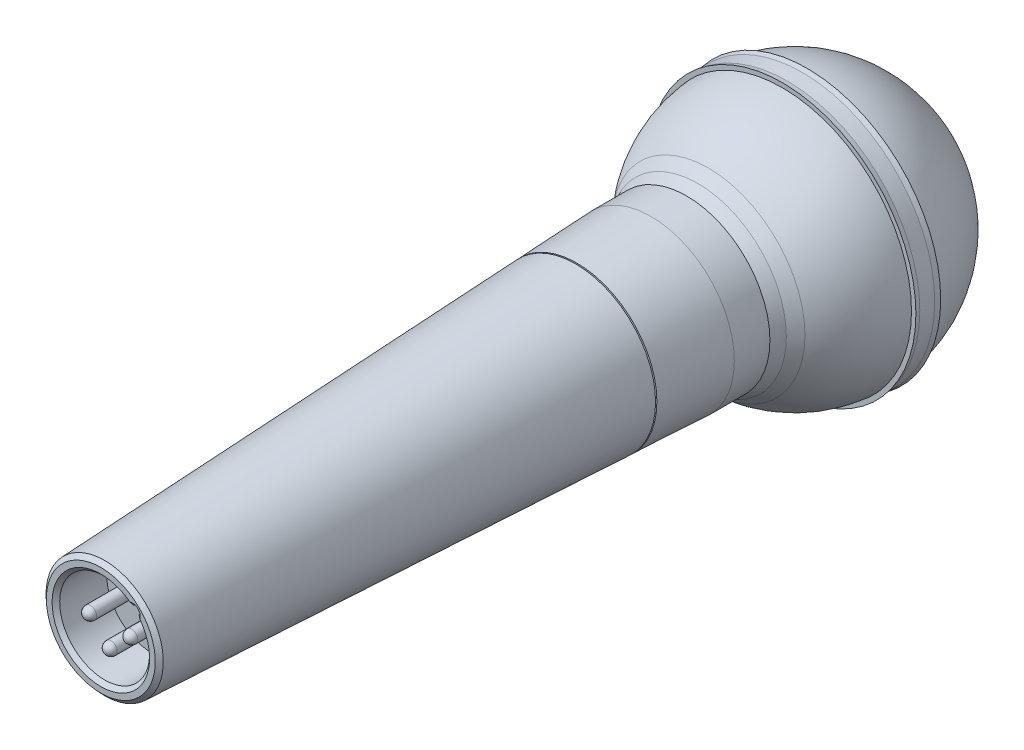
SolidWorks part; units mm, degrees
ref_plane "Front" through (0, 0, 0) normal (0, 0, 1) x (1, 0, 0)
ref_plane "Top" through (0, 0, 0) normal (0, 1, 0) x (1, 0, 0)
ref_plane "Right" through (0, 0, 0) normal (1, 0, 0) x (0, 0, -1)
sketch "Sketch1" plane through (0, 0, 0) normal (0, 1, 0) x (1, 0, 0)
  line L0 (0, 25.5) -> (0, 0) construction
  line L1 (0, 0) -> (0, -25.5) construction
  line L2 (0, 25.5) -> (0, -25.5)
  arc A0 (0, 25.5) -> (0, -25.5) centre (0, 0) ccw
  dimension "D1" = 51
revolve "Revolve2" add sketch "Sketch1" angle 360 about L2
sketch "Sketch2" plane through (0, 0, 0) normal (1, 0, 0) x (0, 0, -1)
  line L0 (-17, 19.0066) -> (-17, -19.0066)
  circle A0 centre (0, 0) radius 25.5 construction
  arc A1 (-17, 19.0066) -> (-17, -19.0066) centre (0, 0) ccw
  dimension "D1" = 17
extrude "Cut-Extrude1" cut sketch "Sketch2" against normal through all both and the other way through all
sketch "Sketch3" plane through (0, 0, 0) normal (1, 0, 0) x (0, 0, -1)
  line L0 (-17, 0) -> (-17, 19.0066)
  line L1 (-17, 19.0066) -> (-17, -19.0066) construction
  line L2 (-17, 19.0066) -> (-19.0544, 17.3966)
  line L3 (-19.0544, 17.3966) -> (-21.2789, 16.3868)
  line L4 (-21.2789, 16.3868) -> (-28.2789, 16.3868)
  line L5 (-28.2789, 16.3868) -> (-42.8513, 15.7288)
  line L6 (-136.5, 11.5) -> (-136.5, 0)
  line L7 (-136.5, 0) -> (-17, 0) construction
  line L8 (-42.8513, 15.7288) -> (-42.8513, 15.2288)
  line L9 (-42.8513, 15.2288) -> (-43.1013, 15.2288)
  line L10 (-43.1013, 15.2288) -> (-43.1013, 15.7175)
  line L11 (-43.1013, 15.7175) -> (-136.5, 11.5)
  line L12 (2.451, 26.2526) -> (1.4793, 26.0451)
  line L13 (-17, 0) -> (-136.5, 0)
  line L14 (-2.426, 26.2526) -> (-2.426, 25.3843)
  line L15 (1.4793, 26.0451) -> (-1.4542, 26.0451)
  line L16 (2.451, 26.2526) -> (2.451, 25.3819)
  line L17 (-2.426, 26.2526) -> (1.2398, 25.4698) construction
  line L18 (-1.2075, 25.4714) -> (2.451, 26.2526) construction
  line L19 (-1.4542, 26.0451) -> (-2.426, 26.2526)
  arc A0 (-17, -19.0066) -> (-17, 19.0066) centre (0, 0) ccw construction
  arc A1 (2.451, 25.3819) -> (-2.426, 25.3843) centre (0, 0) ccw
  arc A2 (-17, 19.0066) -> (-25.5, 0) centre (0, 0) ccw
  point P8 (25.5, 0)
  point P16 (0.0125, 25.7319)
  dimension "D1" = 162
  dimension "D2" = 11.5
  dimension "D3" = 0.25
  dimension "D4" = 0.5
  dimension "D5" = 7
  dimension "D6" = 19.0544
  dimension "D7" = 21.2789
  dimension "D8" = 42.8513
  dimension "D9" = 15.2288
  dimension "D10" = 0.0125
  dimension "D11" = 2.451
  dimension "D12" = 17.3966
  dimension "D13" = 2.426
  dimension "D14" = 25.7319
  dimension "D15" = 26.2526
  dimension "D16" = 1.4793
revolve "Revolve4" add sketch "Sketch3" angle 360 about L7 region at (0, 7.3178, 20.4538) region at (0, 7.1881, 76.5984) region at (0, 25.776, -0.0141)
sketch "Sketch4" plane through (0, 0, 136.5) normal (0, 0, 1) x (1, 0, 0)
  circle A0 centre (0, 0) radius 8.8387
  dimension "D1" = 17.6774
extrude "Cut-Extrude2" cut sketch "Sketch4" against normal blind 10
sketch "Sketch5" plane through (0, 0, 126.5) normal (0, 0, 1) x (1, 0, 0)
  line L0 (-4.05, 0) -> (4.05, 0) construction
  circle A0 centre (-4.05, 0) radius 1.2285
  circle A1 centre (4.05, 0) radius 1.2285
  circle A2 centre (0, -4.0005) radius 1.2285
  point P6 (0, 0)
  point P7 (0, 0)
  dimension "D1" = 2.457
  dimension "D2" = 8.1001
  dimension "D3" = 4.0005
extrude "Boss-Extrude1" add sketch "Sketch5" along normal blind 8 separate body
dome "Dome1" faces to dome 1 distance 1.2285 reverse direction no elliptical dome no face at (-2.8215, 0, 134.5) parameters "D1"=1.2285
dome "Dome2" faces to dome 1 distance 1.2285 reverse direction no elliptical dome no face at (5.2785, 0, 134.5) parameters "D1"=1.2285
dome "Dome3" faces to dome 1 distance 1.2285 reverse direction no elliptical dome no face at (1.2285, -4.0005, 134.5) parameters "D1"=1.2285
sketch "Sketch6" plane through (0, 0, 136.5) normal (0, 0, 1) x (1, 0, 0)
  line L0 (6.2499, 6.2499) -> (0, 0) construction
  line L1 (0, 0) -> (8.8387, 0) construction
  circle A0 centre (6.2499, 6.2499) radius 0.75
  circle A1 centre (0, 0) radius 8.8387 construction
  dimension "D1" = 1.5
  dimension "D2" = 45
extrude "Cut-Extrude4" cut sketch "Sketch6" against normal up to surface (10 mm away) up to face at (8.8387, 0, 126.5)
chamfer "Chamfer1" distance 0.75 angle 45 3 edges at (6.7803, 6.7803, 136.5) (-6.2499, -6.2499, 136.5) (11.5, 0, 136.5) first distance on face at (0.2652, 0.2652, 136.5) first distance on face at (11.5, 0, 136.5)
